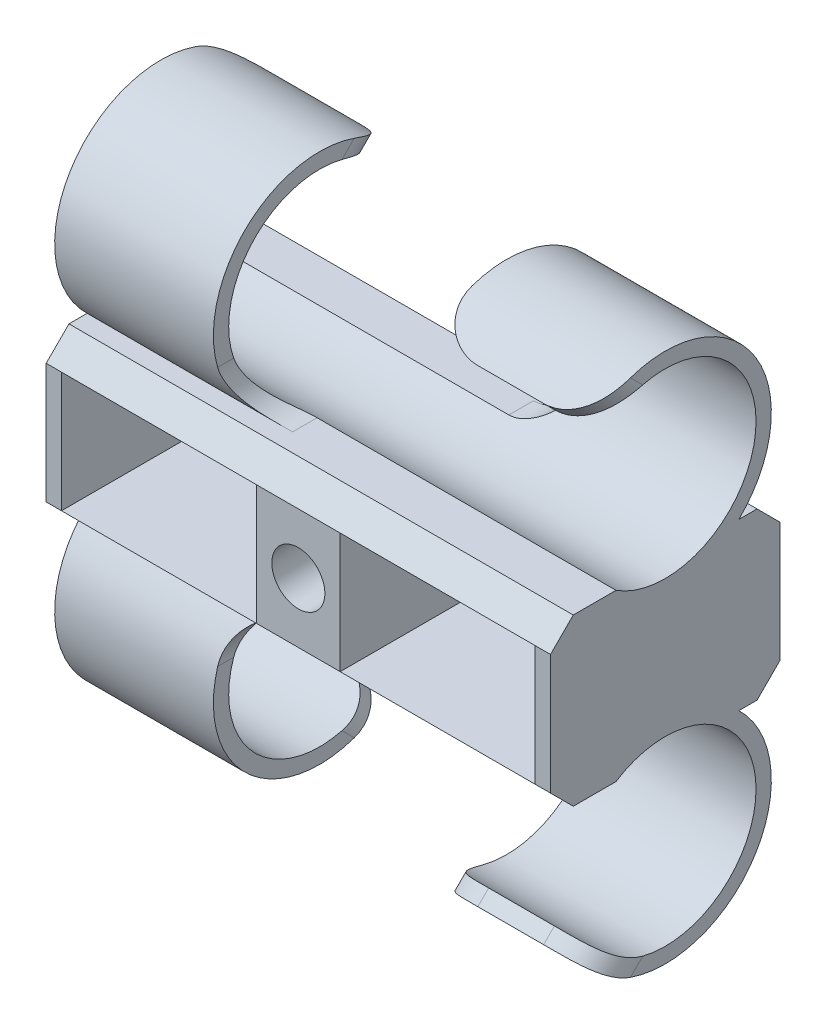
SolidWorks part; units mm, degrees
material "PVC Rigid"
ref_plane "Front" through (0, 0, 0) normal (0, 0, 1) x (1, 0, 0)
ref_plane "Top" through (0, 0, 0) normal (0, 1, 0) x (1, 0, 0)
ref_plane "Right" through (0, 0, 0) normal (1, 0, 0) x (0, 0, -1)
sketch "Sketch2" plane through (0, 0, 0) normal (1, 0, 0) x (0, 0, -1)
  line L0 (0, -19.05) -> (0, 19.05) construction
  line L1 (0, 31.75) -> (0, -31.75) construction
  line L2 (-8.8135, 9.906) -> (-10.9918, 9.906)
  line L3 (-13.716, 7.1818) -> (-13.716, 0)
  line L4 (-13.716, 0) -> (13.716, 0)
  line L5 (13.716, 0) -> (13.716, 7.1818)
  line L6 (13.716, 7.1818) -> (10.9918, 9.906)
  line L7 (10.9918, 9.906) -> (8.8135, 9.906)
  line L8 (-10.9918, 9.906) -> (-13.716, 7.1818)
  line L9 (-10.9918, 9.906) -> (-10.9918, -9.906) construction
  line L10 (-13.716, 7.1818) -> (-13.716, -7.1818) construction
  circle A0 centre (0, 19.05) radius 11.1125 construction
  circle A1 centre (0, 19.05) radius 10.8712
  arc A3 (8.8135, 9.906) -> (-8.8135, 9.906) centre (0, 19.05) ccw
  circle A4 centre (0, 19.05) radius 12.7 construction
  point P5 (-10.9918, 0)
  point P13 (6.7405, 12.4748)
  dimension "D1" = 45
  dimension "D2" = 14.3637
extrude "Boss-Extrude2" add sketch "Sketch2" along normal mid plane 60.325 separate body
sketch "Sketch3" plane through (0, 0, 0) normal (1, 0, 0) x (0, 0, -1)
  line L1 (-8.8135, 9.906) -> (-5.8796, 9.906)
  line L2 (5.8796, 9.906) -> (8.8135, 9.906)
  line L3 (-8.8135, 9.906) -> (-10.9918, 9.906) construction
  line L4 (10.9918, 9.906) -> (8.8135, 9.906) construction
  arc A0 (8.8135, 9.906) -> (-8.8135, 9.906) centre (0, 19.05) ccw construction
  arc A1 (8.8135, 9.906) -> (-8.8135, 9.906) centre (0, 19.05) ccw
  circle A3 centre (0, 19.05) radius 10.8712 construction
  arc A4 (5.8796, 9.906) -> (-5.8796, 9.906) centre (0, 19.05) ccw
extrude "Cut-Extrude1" cut sketch "Sketch3" along normal mid plane 22.352
sketch "Sketch4" plane through (0, 0, 0) normal (1, 0, 0) x (0, 0, -1)
  line L0 (-7.6871, 26.7371) -> (-8.9803, 28.0303)
  line L1 (-8.8135, 9.906) -> (-10.9918, 9.906) construction
  line L2 (-8.8135, 9.906) -> (-5.8796, 9.906)
  line L3 (0, 31.75) -> (0, -31.75) construction
  arc A0 (8.8135, 9.906) -> (-8.8135, 9.906) centre (0, 19.05) ccw construction
  arc A1 (-8.9803, 28.0303) -> (-8.8135, 9.906) centre (0, 19.05) ccw
  circle A2 centre (0, 19.05) radius 10.8712 construction
  arc A3 (-7.6871, 26.7371) -> (-5.8796, 9.906) centre (0, 19.05) ccw
  dimension "D1" = 45
extrude "Cut-Extrude2" cut sketch "Sketch4" along normal through all
ref_axis "Axis1" through (0, 34.925, 0) along (0, -1, 0)
pattern_circular "CirPattern1" count 2 over 360 about axis through (0, 34.925, 0) along (0, -1, 0) of "Cut-Extrude2"
fillet "Fillet1" radius 5.5562 4 edges at (-30.1625, 27.3837, -8.3337) (-11.176, 27.3837, -8.3337) (11.176, 27.3837, 8.3337) (30.1625, 27.3837, 8.3337)
mirror "Mirror1" about plane through (0, 0, 0) normal (0, 1, 0) of bodies 115
sketch "Sketch5" plane through (0, 0, 0) normal (0, 0, -1) x (-1, 0, 0)
  circle A0 centre (0, 0) radius 3.175
  dimension "Mounting Hole Dia" = 6.35
extrude "Cut-Extrude3" cut sketch "Sketch5" against normal through all and the other way through all
sketch "Sketch6" plane through (0, 0, -13.716) normal (0, 0, -1) x (-1, 0, 0)
  circle A0 centre (0, 0) radius 6.223
  dimension "G" = 12.446
extrude "Cut-Extrude4" cut sketch "Sketch6" against normal through all draft 45
sketch "Sketch7" plane through (0, 0, 13.716) normal (0, 0, 1) x (1, 0, 0)
  line L0 (30.1625, 7.1818) -> (-30.1625, 7.1818) construction
  line L1 (-28.3337, 7.1818) -> (-5.0038, 7.1818)
  line L2 (-28.3337, 7.1818) -> (-28.3337, -7.1819)
  line L3 (-28.3337, -7.1819) -> (-5.0038, -7.1819)
  line L4 (-5.0038, 7.1818) -> (-5.0038, -7.1819)
  line L5 (30.1625, -7.1819) -> (-30.1625, -7.1819) construction
  line L6 (28.3337, 7.1818) -> (5.0038, 7.1818)
  line L7 (28.3337, 7.1818) -> (28.3337, -7.1819)
  line L8 (28.3337, -7.1819) -> (5.0038, -7.1819)
  line L9 (5.0038, 7.1818) -> (5.0038, -7.1819)
  line L10 (-30.1625, 7.1818) -> (-30.1625, -7.1819) construction
  circle A0 centre (0, 0) radius 5.0038 construction
  circle A1 centre (0, 0) radius 3.175 construction
  dimension "D1" = 1.8288
  dimension "D2" = 1.8288
extrude "Cut-Extrude5" cut sketch "Sketch7" against normal offset from surface (23.7744 mm away) 3.6576 up to face at (0, 6.223, -13.716)
fillet "Fillet2" radius 5.588 4 edges at (11.176, -9.906, -7.3466) (-11.176, -9.906, 7.3466) (11.176, 9.906, -7.3466) (-11.176, 9.906, 7.3466)
equation "\"D2@Sketch2\" = \"E@Sketch2\" * .725"
equation "\"D1@Fillet1\" = \"ID Min@Sketch2\" * .25"
equation "\"D1@Sketch7\" = \"Thickness@Sketch2\""
equation "\"D2@Sketch7\" = \"Thickness@Sketch2\""
equation "\"D1@Cut-Extrude5\" = \"Thickness@Sketch2\" * 2"
equation "\"D1@Fillet2\" = \"D@Cut-Extrude1\" * .25"
